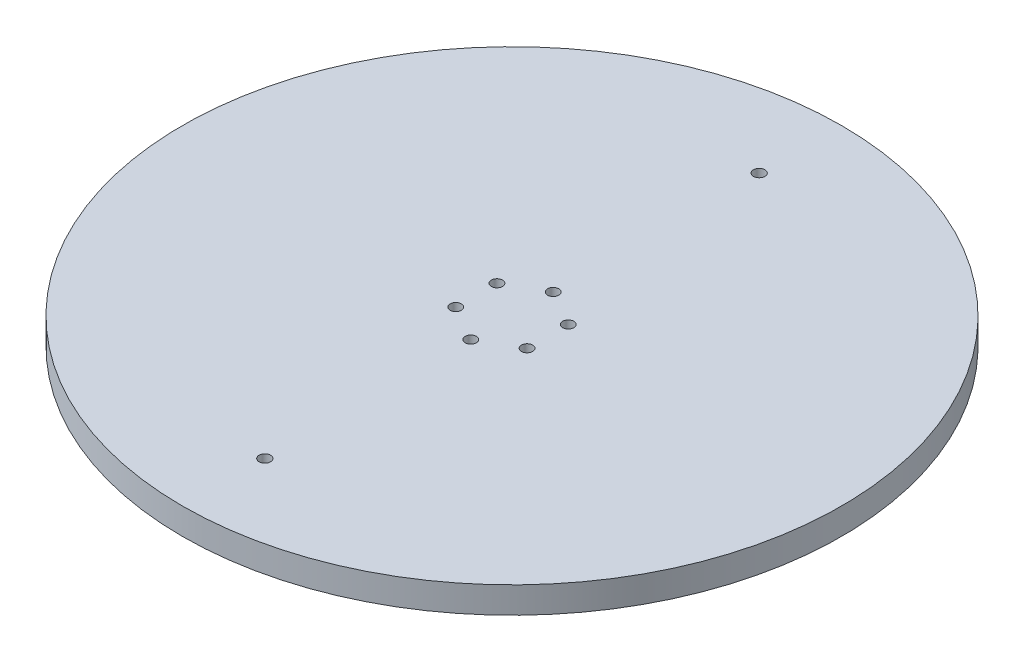
SolidWorks part; units mm, degrees
material "Plain Carbon Steel"
ref_plane "Front Plane" through (0, 0, 0) normal (0, 0, 1) x (1, 0, 0)
ref_plane "Top Plane" through (0, 0, 0) normal (0, 1, 0) x (1, 0, 0)
ref_plane "Right Plane" through (0, 0, 0) normal (1, 0, 0) x (0, 0, -1)
ref_axis "Axis1" through (0, -43.5149, 0) along (0, 1, 0)
sketch "Sketch1" plane through (0, 0, 0) normal (0, 1, 0) x (1, 0, 0)
  circle A0 centre (0, 0) radius 200
  dimension "D1" = 400
extrude "Boss-Extrude1" add sketch "Sketch1" along normal blind 16
hole_wizard "M8 Tapped Hole1" positions "Sketch2" profile "Sketch3" tap size "M8" standard "ISO" end condition through all
sketch "Sketch2" plane through (0, 16, 0) normal (0, 1, 0) x (1, 0, 0)
  line L0 (0, -44.7868) -> (0, 44.7868) construction
  circle A0 centre (0, 0) radius 25 construction
  point P0 (0, 25)
  dimension "D1" = 50
sketch "Sketch3" plane through (0, 16, -25) normal (1, 0, 0) x (0, 0, 1)
  line L0 (0, 0) -> (0, 16)
  line L1 (0, 16) -> (3.4, 16)
  line L2 (3.4, 16) -> (3.4, 0)
  line L5 (3.4, 0) -> (0, 0)
  line L11 (0, -6.35) -> (0, 107.95) construction
  dimension "Thru Tap Drill Dia." = 6.8
  dimension "Thru Tap Drill Depth" = 16
cosmetic thread "Hole Thread4"
pattern_circular "CirPattern1" count 6 over 360 about axis through (0, -43.5149, 0) along (0, 1, 0) of "M8 Tapped Hole1"
cosmetic thread "Hole Thread5"
cosmetic thread "Hole Thread6"
cosmetic thread "Hole Thread7"
cosmetic thread "Hole Thread8"
cosmetic thread "Hole Thread9"
sketch "Sketch6" plane through (0, 16, 0) normal (0, 1, 0) x (1, 0, 0)
  point P0 (0, 150)
  point P2 (0, -150)
  point P6 (0, 0)
  point P7 (0, 0)
  dimension "D1" = 150
  dimension "D2" = 150
hole_wizard "M8x1.0 Tapped Hole1" positions "Sketch6" profile "Sketch5" tap size "M8x1.0" standard "ANSI Metric" end condition through all
sketch "Sketch5" plane through (0, 16, -150) normal (1, 0, 0) x (0, 0, 1)
  line L0 (0, 0) -> (0, 16)
  line L1 (0, 16) -> (3.5, 16)
  line L2 (3.5, 16) -> (3.5, 0)
  line L5 (3.5, 0) -> (0, 0)
  line L11 (0, -6.35) -> (0, 107.95) construction
  dimension "Thru Tap Drill Dia." = 7
  dimension "Thru Tap Drill Depth" = 16
cosmetic thread "Hole Thread10"
cosmetic thread "Hole Thread11"
